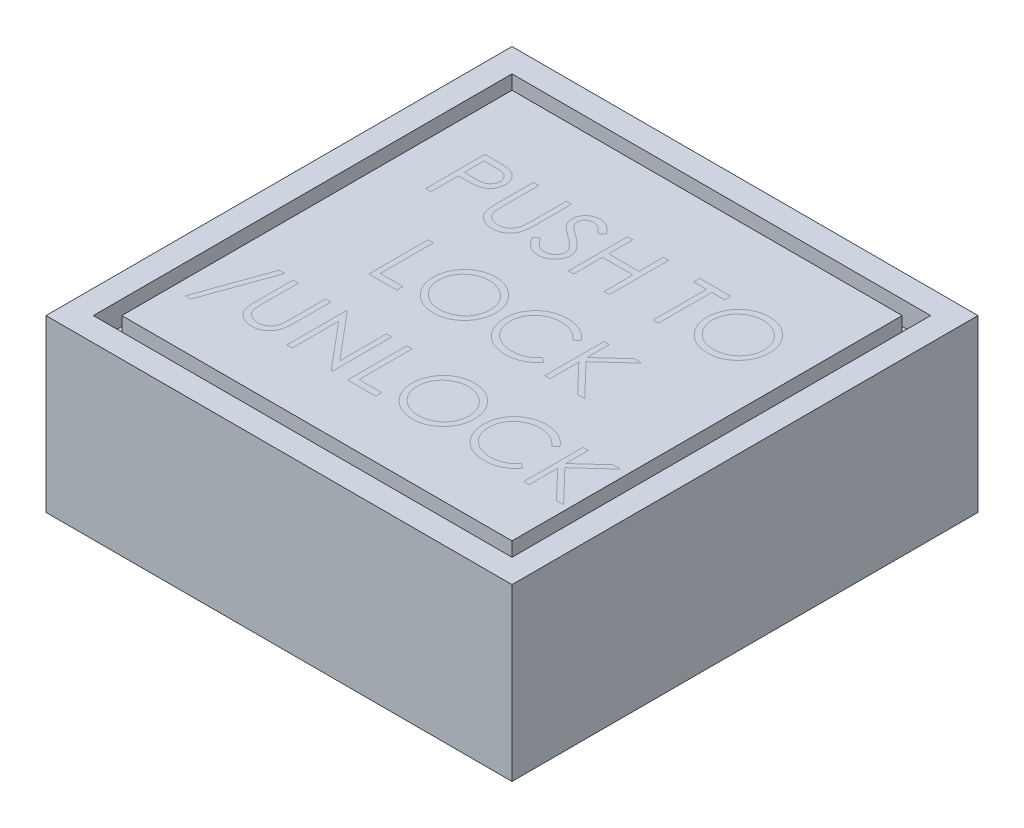
SolidWorks part; units mm, degrees
material "Stainless Steel (ferritic)"
ref_plane "Front Plane" through (0, 0, 0) normal (0, 0, 1) x (1, 0, 0)
ref_plane "Back of Button Plane" through (0, 0, 0) normal (0, 1, 0) x (1, 0, 0)
ref_plane "Right Plane" through (0, 0, 0) normal (1, 0, 0) x (0, 0, -1)
sketch "Sketch1" plane through (0, 0, 0) normal (0, 1, 0) x (1, 0, 0)
  line L1 (0, 0) -> (124.968, 0)
  line L2 (0, 0) -> (0, 124.968)
  line L3 (0, 124.968) -> (124.968, 124.968)
  line L4 (124.968, 0) -> (124.968, 124.968)
  dimension "D1" = 124.968
  dimension "D2" = 124.968
extrude "Boss-Extrude1" add sketch "Sketch1" along normal blind 45.72
sketch "Sketch4" plane through (0, 45.72, 0) normal (0, 1, 0) x (1, 0, 0)
  line L8 (6.35, 118.618) -> (6.35, 6.35)
  line L9 (6.35, 6.35) -> (118.618, 6.35)
  line L10 (118.618, 6.35) -> (118.618, 118.618)
  line L11 (118.618, 118.618) -> (6.35, 118.618)
  line L12 (6.35, 118.618) -> (6.35, 6.35)
  line L13 (6.35, 6.35) -> (118.618, 6.35)
  line L14 (118.618, 6.35) -> (118.618, 118.618)
  line L15 (118.618, 118.618) -> (6.35, 118.618)
  dimension "D1" = 6.35
extrude "Cut-Extrude1" cut sketch "Sketch4" against normal blind 6.35
sketch "Sketch6" plane through (0, 39.37, 0) normal (0, 1, 0) x (1, 0, 0)
  line L8 (114.808, 10.16) -> (114.808, 114.808)
  line L9 (10.16, 10.16) -> (114.808, 10.16)
  line L10 (10.16, 114.808) -> (10.16, 10.16)
  line L11 (114.808, 114.808) -> (10.16, 114.808)
  line L12 (114.808, 10.16) -> (114.808, 114.808)
  line L13 (10.16, 10.16) -> (114.808, 10.16)
  line L14 (10.16, 114.808) -> (10.16, 10.16)
  line L15 (114.808, 114.808) -> (10.16, 114.808)
  dimension "D1" = 3.81
extrude "Boss-Extrude2" add sketch "Sketch6" along normal blind 6.35
sketch "Sketch11" plane through (0, 45.72, 0) normal (0, 1, 0) x (1, 0, 0)
  text T0 " PUSH TO \r\n   LOCK\r\n/UNLOCK" font "Century Gothic" height in points 60
  point P1 (0, 0)
  point P2 (0, 0)
wrap "Wrap1" sketch "Sketch11" wrap type scribe source sketch "Sketch11" face at (62.484, 45.72, -62.484)
